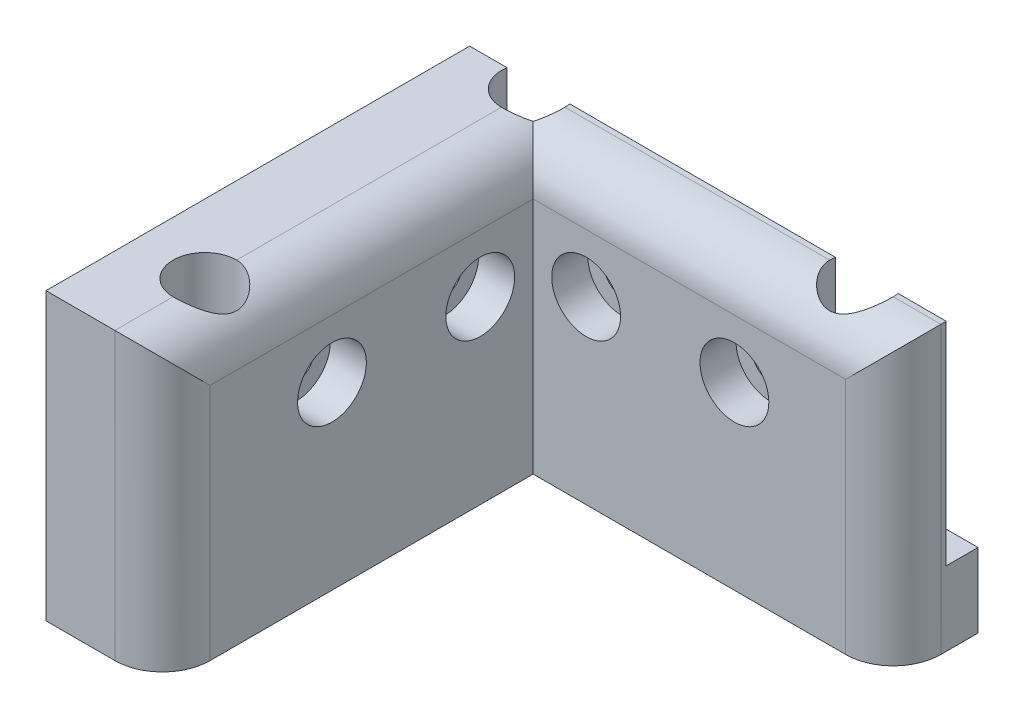
SolidWorks part; units mm, degrees
material "ABS"
ref_plane "Front Plane" through (0, 0, 0) normal (0, 0, 1) x (1, 0, 0)
ref_plane "Top Plane" through (0, 0, 0) normal (0, 1, 0) x (1, 0, 0)
ref_plane "Right Plane" through (0, 0, 0) normal (1, 0, 0) x (0, 0, -1)
sketch "Sketch1" plane through (0, 0, 0) normal (0, 1, 0) x (1, 0, 0)
  line L1 (0, 0) -> (45, 0)
  line L2 (0, 0) -> (0, 40)
  line L3 (0, 40) -> (45, 40)
  line L4 (45, 0) -> (45, 40)
  dimension "D1" = 45
  dimension "D2" = 40
extrude "Boss-Extrude1" add sketch "Sketch1" along normal blind 29
sketch "Sketch33" plane through (0, 29, 0) normal (0, 1, 0) x (1, 0, 0)
  line L0 (0, 40) -> (0, 0) construction
  line L1 (45, 0) -> (11, 0)
  line L2 (45, 0) -> (45, 35)
  line L3 (45, 35) -> (11, 35)
  line L4 (11, 0) -> (11, 35)
  line L5 (45, 40) -> (0, 40) construction
  dimension "D1" = 11
  dimension "D2" = 5
extrude "Cut-Extrude7" cut sketch "Sketch33" against normal through all
sketch "Sketch39" plane through (0, 0, -40) normal (0, 0, -1) x (-1, 0, 0)
  line L0 (0, 29) -> (0, 0) construction
  line L1 (-45, 0) -> (0, 0)
  line L2 (-45, 0) -> (-45, 9)
  line L3 (-45, 9) -> (0, 9)
  line L4 (0, 0) -> (0, 9)
  dimension "D1" = 9
extrude "Boss-Extrude2" add sketch "Sketch39" along normal blind 3
sketch "Sketch21" plane through (0, 29, 0) normal (0, 1, 0) x (1, 0, 0)
  line L0 (45, 40) -> (0, 40) construction
  circle A1 centre (6.5, 39.5) radius 1.75
  circle A2 centre (6.5, 8.5) radius 1.75
  circle A3 centre (37.5, 39.5) radius 1.75
  dimension "D3" = 0.5
  dimension "D4" = 3.5
  dimension "D7" = 3.5
  dimension "D8" = 3.5
  dimension "D1" = 0.5
  dimension "D2" = 31
extrude "Cut-Extrude6" cut sketch "Sketch21" against normal through all both and the other way through all
sketch "Sketch34" plane through (0, 29, 0) normal (0, 1, 0) x (1, 0, 0)
  circle A0 centre (6.5, 8.5) radius 3
  circle A1 centre (6.5, 39.5) radius 3
  circle A2 centre (37.5, 39.5) radius 3
  dimension "D1" = 6
  dimension "D2" = 6
  dimension "D3" = 6
extrude "Cut-Extrude8" cut sketch "Sketch34" against normal blind 23
hole_wizard "CBORE for M3 Hex Socket Head Cap Screw1" positions "Sketch35" profile "Sketch36" counterbore size "M3" standard "ISO" end condition through all
sketch "Sketch35" plane through (11, 0, 0) normal (1, 0, 0) x (0, 0, -1)
  line L1 (0, 0) -> (0, 29) construction
  line L2 (35, 0) -> (35, 29) construction
  line L3 (35, 29) -> (0, 29) construction
  point P0 (16, 19)
  point P2 (30, 19)
  dimension "D1" = 10
  dimension "D2" = 10
  dimension "D3" = 16
  dimension "D4" = 5
sketch "Sketch36" plane through (11, 19, -16) normal (0, 1, 0) x (0, 0, -1)
  line L0 (0, 0) -> (0, 11)
  line L1 (0, 11) -> (1.7, 11)
  line L3 (1.7, 11) -> (1.7, 3.4)
  line L4 (1.7, 3.4) -> (3.25, 3.4)
  line L5 (3.25, 3.4) -> (3.25, 0)
  line L7 (3.25, 0) -> (0, 0)
  line L11 (0, -6.35) -> (0, 107.95) construction
  dimension "Thru Hole Dia." = 3.4
  dimension "Thru Hole Depth" = 11
  dimension "C'Bore Dia." = 6.5
  dimension "C'Bore Depth" = 3.4
hole_wizard "CBORE for M3 Hex Socket Head Cap Screw2" positions "Sketch37" profile "Sketch38" counterbore size "M3" standard "ISO" end condition through all
sketch "Sketch37" plane through (0, 0, -35) normal (0, 0, 1) x (1, 0, 0)
  line L1 (11, 0) -> (11, 29) construction
  line L2 (45, 0) -> (45, 29) construction
  line L3 (45, 29) -> (11, 29) construction
  point P0 (16, 19)
  point P2 (30, 19)
  dimension "D1" = 10
  dimension "D2" = 10
  dimension "D3" = 5
  dimension "D4" = 15
sketch "Sketch38" plane through (16, 19, -35) normal (1, 0, 0) x (0, -1, 0)
  line L0 (0, 0) -> (0, 8)
  line L1 (0, 8) -> (1.7, 8)
  line L3 (1.7, 8) -> (1.7, 3.4)
  line L4 (1.7, 3.4) -> (3.25, 3.4)
  line L5 (3.25, 3.4) -> (3.25, 0)
  line L7 (3.25, 0) -> (0, 0)
  line L11 (0, -6.35) -> (0, 107.95) construction
  dimension "Thru Hole Dia." = 3.4
  dimension "Thru Hole Depth" = 8
  dimension "C'Bore Dia." = 6.5
  dimension "C'Bore Depth" = 3.4
fillet "Fillet1" radius 4.5 4 edges at (11, 14.5, 0) (45, 14.5, -35) (28, 29, -35) (11, 29, -17.5)
sketch "Sketch40" plane through (0, 0, 0) normal (-1, 0, 0) x (0, 0, 1)
  line L0 (-43, 0) -> (-43, 9) construction
  line L1 (-43, 2) -> (0, 2)
  line L2 (-43, 2) -> (-43, 0)
  line L3 (-43, 0) -> (0, 0)
  line L4 (0, 2) -> (0, 0)
  dimension "D1" = 2
extrude "Cut-Extrude9" cut sketch "Sketch40" against normal through all
sketch "Sketch41" plane through (0, 29, 0) normal (0, 1, 0) x (1, 0, 0)
  line L0 (3.542, 40) -> (0, 40) construction
  line L1 (0, 0) -> (6, 0)
  line L2 (0, 0) -> (0, 40)
  line L3 (0, 40) -> (6, 40)
  line L4 (6, 0) -> (6, 40)
  dimension "D1" = 6
extrude "Cut-Extrude10" [suppressed] cut sketch "Sketch41" against normal blind 20
mirror "Mirror1" [suppressed] of bodies 125 122
delete or keep bodies "Body-Delete/Keep 1" [suppressed] type delete bodies bodies 125
